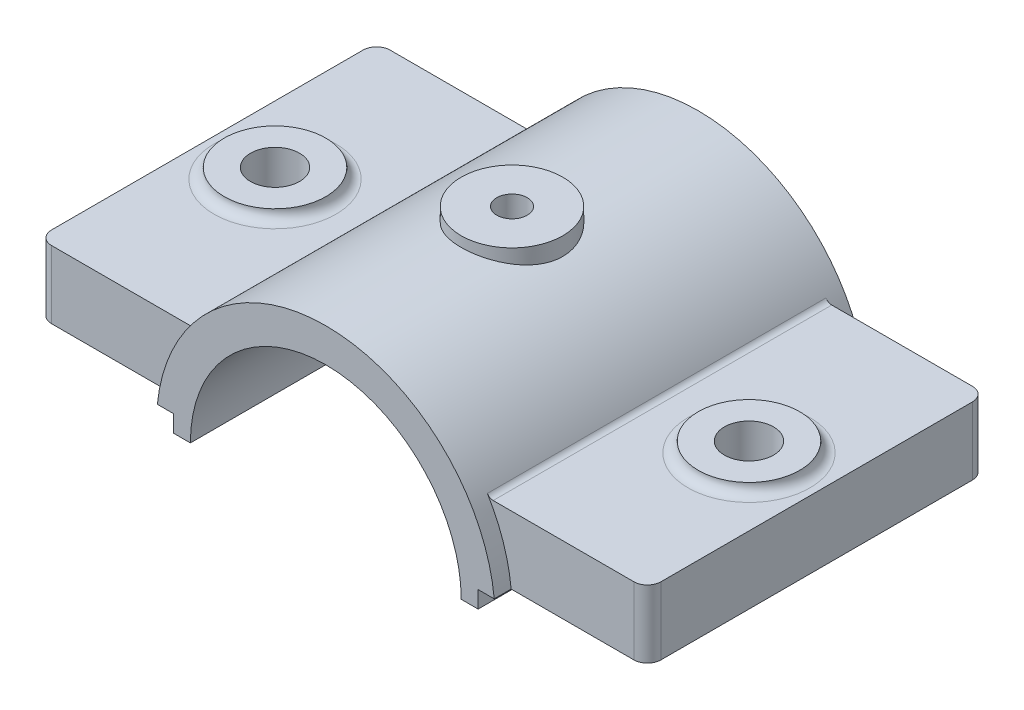
SolidWorks part; units mm, degrees
ref_plane "Front Plane" through (0, 0, 0) normal (0, 0, 1) x (1, 0, 0)
ref_plane "Top Plane" through (0, 0, 0) normal (0, 1, 0) x (1, 0, 0)
ref_plane "Right Plane" through (0, 0, 0) normal (1, 0, 0) x (0, 0, -1)
sketch "Sketch1" plane through (0, 0, 0) normal (0, 0, 1) x (1, 0, 0)
  line L0 (-40, 0) -> (40, 0) construction
  line L1 (-40, 0) -> (-45, 0)
  line L2 (-45, 0) -> (-45, 5)
  line L3 (-45, 5) -> (-90, 5)
  line L4 (40, 0) -> (45, 0)
  line L5 (45, 0) -> (45, 5)
  line L6 (45, 5) -> (90, 5)
  line L7 (-90, 5) -> (-90, 25)
  line L8 (90, 5) -> (90, 25)
  line L9 (-90, 25) -> (-43.3013, 25)
  line L10 (90, 25) -> (43.3013, 25)
  arc A0 (40, 0) -> (-40, 0) centre (0, 0) ccw
  arc A1 (43.3013, 25) -> (-43.3013, 25) centre (0, 0) ccw
  dimension "D1" = 40
  dimension "D2" = 50
  dimension "D3" = 5
  dimension "D4" = 5
  dimension "D5" = 45
  dimension "D6" = 45
  dimension "D7" = 20
extrude "Boss-Extrude1" add sketch "Sketch1" against normal mid plane 100
sketch "Sketch2" plane through (0, 0, 50) normal (0, 0, 1) x (1, 0, 0)
  line L0 (40, 0) -> (45, 0)
  line L1 (45, 0) -> (45, 5)
  line L2 (45, 5) -> (49.7494, 5)
  line L3 (45, 5) -> (90, 5) construction
  line L4 (-40, 0) -> (-45, 0)
  line L5 (-45, 0) -> (-45, 5)
  line L6 (-45, 5) -> (-49.7494, 5)
  line L7 (-90, 5) -> (-45, 5) construction
  arc A0 (40, 0) -> (-40, 0) centre (0, 0) ccw construction
  arc A1 (40, 0) -> (-40, 0) centre (0, 0) ccw
  arc A3 (49.7494, 5) -> (-49.7494, 5) centre (0, 0) ccw
  dimension "D1" = 100
extrude "Boss-Extrude2" add sketch "Sketch2" along normal blind 5
mirror "Mirror1" about plane through (0, 0, 0) normal (0, 0, 1) of "Boss-Extrude2"
sketch "Sketch3" plane through (0, 25, 0) normal (0, 1, 0) x (1, 0, 0)
  line L0 (-70, 0) -> (70, 0) construction
  circle A0 centre (-70, 0) radius 15
  circle A1 centre (70, 0) radius 15
  dimension "D1" = 30
  dimension "D2" = 30
  dimension "D3" = 140
extrude "Boss-Extrude3" add sketch "Sketch3" along normal blind 3
fillet "Fillet1" radius 3 2 edges at (70, 25, 15) (-70, 25, 15)
hole_wizard "M16x1.5 Tapped Hole1" positions "Sketch5" profile "Sketch6" tap size "M16x1.5" standard "IS" end condition through all
sketch "Sketch5" plane through (0, 28, 0) normal (0, 1, 0) x (1, 0, 0)
  point P0 (-70, 0)
  point P3 (70, 0)
sketch "Sketch6" plane through (-70, 28, 0) normal (1, 0, 0) x (0, 0, 1)
  line L0 (0, 0) -> (0, 28)
  line L1 (0, 28) -> (7.25, 28)
  line L2 (7.25, 28) -> (7.25, 0)
  line L5 (7.25, 0) -> (0, 0)
  line L11 (0, -6.35) -> (0, 107.95) construction
  dimension "Thru Tap Drill Dia." = 14.5
  dimension "Thru Tap Drill Depth" = 28
ref_plane "Plane2" through (0, 53, 0) normal (0, -1, 0) x (-1, 0, 0)
sketch "Sketch11" plane through (0, 53, 0) normal (0, -1, 0) x (-1, 0, 0)
  circle A0 centre (0, 0) radius 15
  dimension "D1" = 30
extrude "Boss-Extrude6" add sketch "Sketch11" along normal up to next
hole_wizard "M10x1.0 Tapped Hole1" positions "Sketch12" profile "Sketch13" tap size "M10x1.0" standard "ANSI Metric" end condition through all
sketch "Sketch12" plane through (0, 53, 0) normal (0, 1, 0) x (1, 0, 0)
  point P0 (0, 0)
sketch "Sketch13" plane through (0, 53, 0) normal (1, 0, 0) x (0, 0, 1)
  line L0 (0, 0) -> (0, 53)
  line L1 (0, 53) -> (4.5, 53)
  line L2 (4.5, 53) -> (4.5, 0)
  line L5 (4.5, 0) -> (0, 0)
  line L11 (0, -6.35) -> (0, 107.95) construction
  dimension "Thru Tap Drill Dia." = 9
  dimension "Thru Tap Drill Depth" = 53
ref_plane "Plane4" through (0, 43, 0) normal (0, -1, 0) x (-1, 0, 0)
sketch "Sketch15" plane through (0, 43, 0) normal (0, -1, 0) x (-1, 0, 0)
  circle A0 centre (0, 0) radius 8
  dimension "D1" = 16
extrude "Cut-Extrude1" cut sketch "Sketch15" along normal through all
fillet "Fillet2" radius 2 2 edges at (-43.3013, 25, 0) (43.3013, 25, 0)
fillet "Fillet3" radius 4 4 edges at (90, 15, 50) (90, 15, -50) (-90, 15, 50) (-90, 15, -50)
